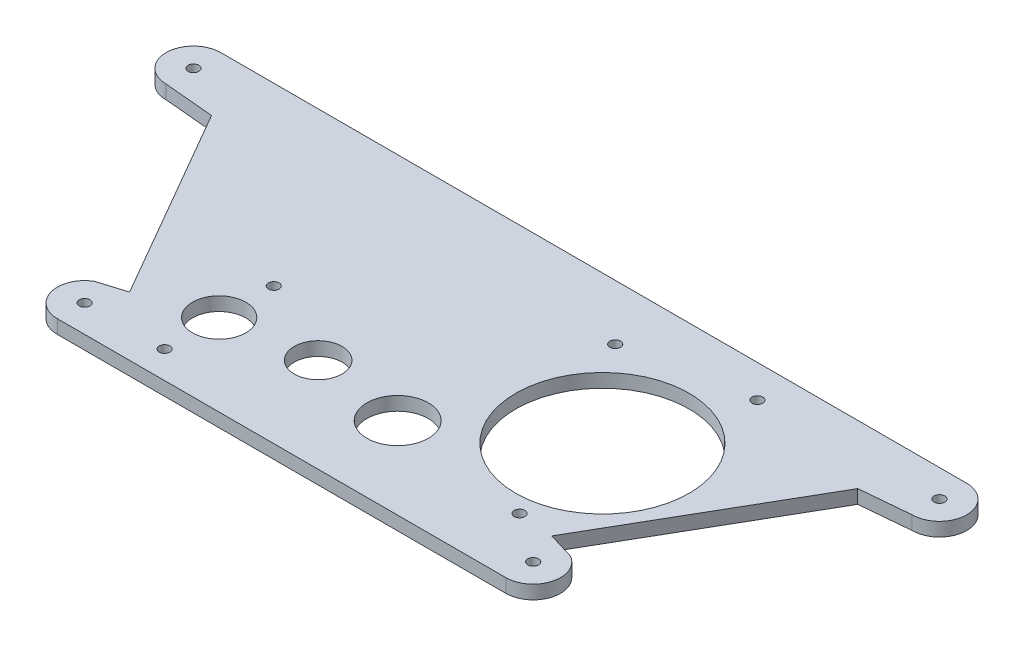
SolidWorks part; units mm, degrees
ref_plane "Front Plane" through (0, 0, 0) normal (0, 0, 1) x (1, 0, 0)
ref_plane "Top Plane" through (0, 0, 0) normal (0, 1, 0) x (1, 0, 0)
ref_plane "Right Plane" through (0, 0, 0) normal (1, 0, 0) x (0, 0, -1)
sketch "Sketch1" plane through (0, 0, 0) normal (0, 1, 0) x (1, 0, 0)
  line L0 (-67.1329, -34.491) -> (-26.9117, -28.6714) construction
  line L1 (-195.4757, -72.591) -> (195.4757, -72.591)
  line L2 (-195.4757, -72.591) -> (-195.4757, 72.591)
  line L3 (-186.1787, 59.891) -> (186.1787, 59.891)
  line L4 (195.4757, -72.591) -> (195.4757, 72.591)
  line L5 (-195.4757, -72.591) -> (195.4757, 72.591) construction
  line L6 (-195.4757, 72.591) -> (195.4757, -72.591) construction
  line L7 (-26.9117, -28.6714) -> (15.8743, -34.491) construction
  line L8 (15.8743, -34.491) -> (-67.1329, -34.491) construction
  line L9 (15.8743, -34.491) -> (72.644, 3.9852) construction
  line L10 (72.644, 3.9852) -> (-26.9117, -28.6714) construction
  line L11 (-166.1463, 72.591) -> (-82.3255, -72.591)
  line L12 (158.814, 72.591) -> (74.9932, -72.591)
  line L13 (-195.4757, 72.591) -> (-180.811, 72.591)
  line L14 (82.3255, -72.591) -> (166.1463, 72.591)
  line L15 (-180.811, 72.591) -> (-96.9902, -72.591) construction
  line L16 (-195.4757, 72.591) -> (-111.6549, -72.591)
  line L17 (96.9902, -72.591) -> (180.811, 72.591) construction
  line L18 (111.6549, -72.591) -> (195.4757, 72.591)
  line L19 (-173.4787, 47.191) -> (-150.2713, 45.0947)
  line L20 (-110.6726, -48.8924) -> (-98.2005, -45.0947)
  line L21 (0, 72.591) -> (0, -72.591) construction
  line L22 (173.4787, 47.191) -> (150.2713, 45.0947)
  line L23 (110.6726, -48.8924) -> (98.2005, -45.0947)
  line L24 (72.644, 3.9852) -> (35.7109, 46.8482) construction
  line L25 (35.7109, 46.8482) -> (91.2979, 57.4018) construction
  line L26 (91.2979, 57.4018) -> (72.644, 3.9852) construction
  line L27 (72.644, 3.9852) -> (81.6718, -43.5654) construction
  line L28 (-173.4787, 72.591) -> (195.4757, 72.591)
  circle A0 centre (-67.1329, -34.491) radius 12.3825
  circle A1 centre (-67.1329, -34.491) radius 32.2072
  circle A2 centre (-67.1329, -9.091) radius 2.4892
  circle A3 centre (-67.1329, -59.891) radius 2.4892
  circle A4 centre (15.8743, -34.491) radius 14.3002
  circle A5 centre (-26.9117, -28.6714) radius 11.1252
  circle A6 centre (72.644, 3.9852) radius 40.3225
  circle A7 centre (-173.4787, 59.891) radius 2.4892
  circle A8 centre (-104.3226, -59.891) radius 2.4892
  circle A9 centre (-173.4787, 59.891) radius 12.7
  circle A10 centre (-104.3226, -59.891) radius 12.7
  circle A11 centre (104.3226, -59.891) radius 2.4892
  circle A12 centre (104.3226, -59.891) radius 12.7
  circle A13 centre (173.4787, 59.891) radius 2.4892
  circle A14 centre (173.4787, 59.891) radius 12.7
  circle A15 centre (35.7109, 46.8482) radius 2.4892
  circle A16 centre (91.2979, 57.4018) radius 2.4892
  circle A17 centre (81.6718, -43.5654) radius 2.4892
  point P0 (0, 0)
  point P16 (-72.4812, -34.491)
  dimension "D1" = 64.4144
  dimension "D2" = 24.765
  dimension "D3" = 4.9784
  dimension "D4" = 25.4
  dimension "D6" = 12.7
  dimension "D11" = 28.6004
  dimension "D14" = 22.2504
  dimension "D15" = 80.645
  dimension "D17" = 50.8
  dimension "D25" = 4.9784
  dimension "D26" = 4.9784
  dimension "D27" = 12.7
  dimension "D28" = 25.4
  dimension "D30" = 25.4
  dimension "D36" = 4.9784
  dimension "D37" = 4.9784
  dimension "D38" = 4.9784
  dimension "D7" = 25.4
  dimension "D8" = 40.64
  dimension "D9" = 43.18
  dimension "D10" = 83.0072
  dimension "D12" = 68.58
  dimension "D13" = 104.775
  dimension "D16" = 120
  dimension "D18" = 120
  dimension "D19" = 12.7
  dimension "D20" = 6.35
  dimension "D21" = 12.7
  dimension "D22" = 12.7
  dimension "D23" = 12.7
  dimension "D24" = 12.7
  dimension "D29" = 31.75
  dimension "D31" = 31.75
  dimension "D32" = 56.58
  dimension "D33" = 48.4
  dimension "D34" = 150
  dimension "D35" = 10.75
  dimension "D39" = 390.9515
  dimension "D40" = 372.3574
  dimension "D41" = 145.1819
  dimension "D42" = 107.0819
  dimension "D43" = 23.3018
  dimension "D44" = 125.161
  dimension "D5" = 2
extrude "Boss-Extrude1" add sketch "Sketch1" along normal blind 6.35 contours L3 A16 L11 A1 A5 L1 L12 A6 A17 A15 A4 | A9 L19 L11 L3 | A9 L3 A7 | L3 A9 A7 | A9 L11 L28 | A9 L3 L11 | L28 L11 L3 L12 | A14 L3 A13 | L22 A14 L3 L14 | L1 L14 L3 L12 | L28 L12 L3 L14 | L3 A14 L14 | L14 A14 L28 | A14 L3 A13 | A12 L23 A11 | L14 A12 L23 | L1 A12 L14 | A5 A1 A3 A2 A0 | A10 L20 A8 | A10 L1 L11 | A10 L11 L20 region at (-90.4145, 0, 67.9208) region at (-110.493, 0, 70.5784) region at (-173.4787, 0, -54.3278) region at (-80.2961, 0, 6.0972) region at (-12.5567, 0, -6.9871) region at (-173.4787, 0, -65.4541) region at (-159.3373, 0, -50.5787) region at (116.9036, 0, 6.35) region at (-98.9155, 0, 47.5186) region at (-166.9156, 0, -71.2586) region at (-160.3524, 0, -61.5233) region at (90.4145, 0, 67.9208) region at (-3.6662, 0, -66.2898) region at (93.6351, 0, 66.0614) region at (98.9155, 0, 47.5186) region at (158.814, 0, -66.241) region at (160.3524, 0, -61.5233) region at (159.3373, 0, -50.5787) region at (166.9156, 0, -71.2586) region at (173.4787, 0, -54.3278) region at (173.4787, 0, -65.4541)
sketch "Sketch2" plane through (0, 6.35, 0) normal (0, 1, 0) x (1, 0, 0)
  line L0 (-150.2713, 45.0947) -> (-98.2005, -45.0947)
  line L1 (-158.814, 72.591) -> (-74.9932, -72.591)
  line L2 (-173.4787, 72.591) -> (173.4787, 72.591) construction
  line L3 (-104.3226, -72.591) -> (104.3226, -72.591) construction
  line L4 (-155.1478, 66.241) -> (155.1478, 66.241)
  line L5 (-78.6593, -66.241) -> (78.6593, -66.241)
  line L6 (150.2713, 45.0947) -> (98.2005, -45.0947)
  line L7 (158.814, 72.591) -> (74.9932, -72.591)
  line L8 (-26.9117, -28.6714) -> (-26.9117, 66.241) construction
  line L9 (-26.9117, -28.6714) -> (15.8743, -34.491) construction
  line L10 (15.8743, -34.491) -> (72.644, 3.9852) construction
  line L11 (35.7109, 46.8482) -> (35.7109, 66.241) construction
  line L12 (15.8743, -34.491) -> (15.8743, -66.241) construction
  line L13 (-67.1329, -9.091) -> (-110.6258, 66.241) construction
  line L14 (-143.9514, 46.8482) -> (35.7109, 46.8482) construction
  line L15 (-26.9117, -28.6714) -> (-3.1757, -59.7979) construction
  line L16 (-145.7845, 50.0232) -> (23.4142, 50.0232)
  line L17 (-142.1183, 43.6732) -> (23.4142, 43.6732)
  line L18 (-114.292, 66.241) -> (-77.5651, 2.6281)
  line L19 (-106.9596, 66.241) -> (-70.9535, 3.8765)
  line L20 (-30.0867, 66.241) -> (-30.0867, -11.487)
  line L21 (-23.7367, 66.241) -> (-23.7367, -11.487)
  line L22 (-19.0162, -44.2612) -> (-13.1568, -51.9451)
  line L23 (-8.1074, -48.0946) -> (-13.9669, -40.4108)
  line L24 (-9.4562, -27.8414) -> (-3.9163, -28.5949)
  line L25 (-10.3121, -34.1334) -> (-4.7721, -34.887)
  line L26 (12.6993, -54.8956) -> (12.6993, -66.241)
  line L27 (19.0493, -54.8956) -> (19.0493, -66.241)
  line L28 (30.9837, -20.4149) -> (32.3173, -19.5111)
  line L29 (34.5464, -25.6713) -> (35.8799, -24.7675)
  line L30 (32.5359, 59.145) -> (32.5359, 66.241)
  line L31 (38.8859, 59.145) -> (38.8859, 66.241)
  line L32 (36.5245, 66.241) -> (36.5245, -72.591) construction
  line L33 (30.1745, 66.241) -> (30.1745, -72.591) construction
  line L34 (30.1745, -19.5935) -> (-23.7367, 66.241) construction
  line L35 (18.2805, -13.9814) -> (-32.1059, 66.241) construction
  line L36 (-17.9315, 43.6732) -> (18.2805, -13.9814)
  line L37 (0.1745, 14.8459) -> (-23.7367, -0.1724) construction
  line L38 (-1.8899, 13.5493) -> (-1.8899, 66.241) construction
  line L39 (-1.8899, 13.5493) -> (-26.9117, -28.6714) construction
  line L40 (-1.8899, 13.5493) -> (15.8743, -34.491) construction
  line L41 (-5.0649, 66.241) -> (-5.0649, 22.5296)
  line L42 (1.2851, 66.241) -> (1.2851, 22.5296)
  line L43 (-9.1997, 7.4426) -> (-20.8819, -12.2694)
  line L44 (-3.737, 4.2051) -> (-15.4192, -15.5069)
  line L45 (-1.7532, 4.0253) -> (5.8195, -16.454)
  line L46 (4.2026, 6.2276) -> (11.7754, -14.2517)
  circle A0 centre (-67.1329, -34.491) radius 38.5572
  circle A1 centre (72.644, 3.9852) radius 46.6725
  circle A2 centre (-26.9117, -28.6714) radius 17.4752
  circle A3 centre (15.8743, -34.491) radius 20.6502
  circle A4 centre (35.7109, 46.8482) radius 12.7
  circle A5 centre (91.2979, 57.4018) radius 12.7
  circle A6 centre (81.6718, -43.5654) radius 12.7
  circle A7 centre (-99.4294, 46.8482) radius 2.1526
  circle A8 centre (-26.9117, 46.8482) radius 2.1527
  circle A9 centre (-99.4294, 46.8482) radius 9.525
  circle A10 centre (-26.9117, 46.8482) radius 9.525
  circle A11 centre (-3.1757, -59.7979) radius 12.7
  circle A12 centre (-3.1757, -59.7979) radius 2.1527
  circle A13 centre (-1.8899, 13.5493) radius 9.525
  circle A14 centre (-1.8899, 13.5493) radius 2.1526
  point P96 (-17.9315, 43.6732)
  dimension "D1" = 77.1144
  dimension "D4" = 93.345
  dimension "D7" = 34.9504
  dimension "D8" = 41.3004
  dimension "D9" = 25.4
  dimension "D10" = 25.4
  dimension "D11" = 25.4
  dimension "D12" = 4.3053
  dimension "D13" = 4.3053
  dimension "D14" = 19.05
  dimension "D15" = 19.05
  dimension "D17" = 25.4
  dimension "D18" = 4.3053
  dimension "D28" = 75.5196
  dimension "D31" = 19.05
  dimension "D35" = 4.3053
  dimension "D2" = 6.35
  dimension "D3" = 6.35
  dimension "D5" = 6.35
  dimension "D6" = 6.35
  dimension "D16" = 19.05
  dimension "D19" = 12.793
  dimension "D20" = 6.35
  dimension "D21" = 6.35
  dimension "D22" = 6.35
  dimension "D23" = 6.35
  dimension "D24" = 6.35
  dimension "D25" = 6.35
  dimension "D26" = 6.35
  dimension "D27" = 6.35
  dimension "D29" = 1.7536
  dimension "D30" = 6.35
  dimension "D32" = 6.35
  dimension "D33" = 6.35
  dimension "D34" = 6.35
extrude "Cut-Extrude1" [suppressed] cut sketch "Sketch2" against normal through all contours A9 L17 L1 A0 L18 | A9 L18 L4 L1 L16 | A10 L20 L4 L19 A9 L16 | A10 L17 A9 L19 A0 A2 L20 | A10 L21 A2 L24 A3 L28 A1 A4 L17 | A5 L4 L31 A4 A1 | A5 A1 L7 L4 | A6 A1 L29 A3 L27 L5 L7 | A11 L22 A2 A0 L5 | A7 | A8 | A12 | A10 L16 L41 L4 L21 | L41 L17 L36 | A13 L41 L36 A10 L21 A2 L43 | A13 L44 A2 L24 A3 L45 | A13 L46 A3 L36 | A4 L30 L4 L42 L16 | A14
fillet "Fillet1" [suppressed] radius 2.54
